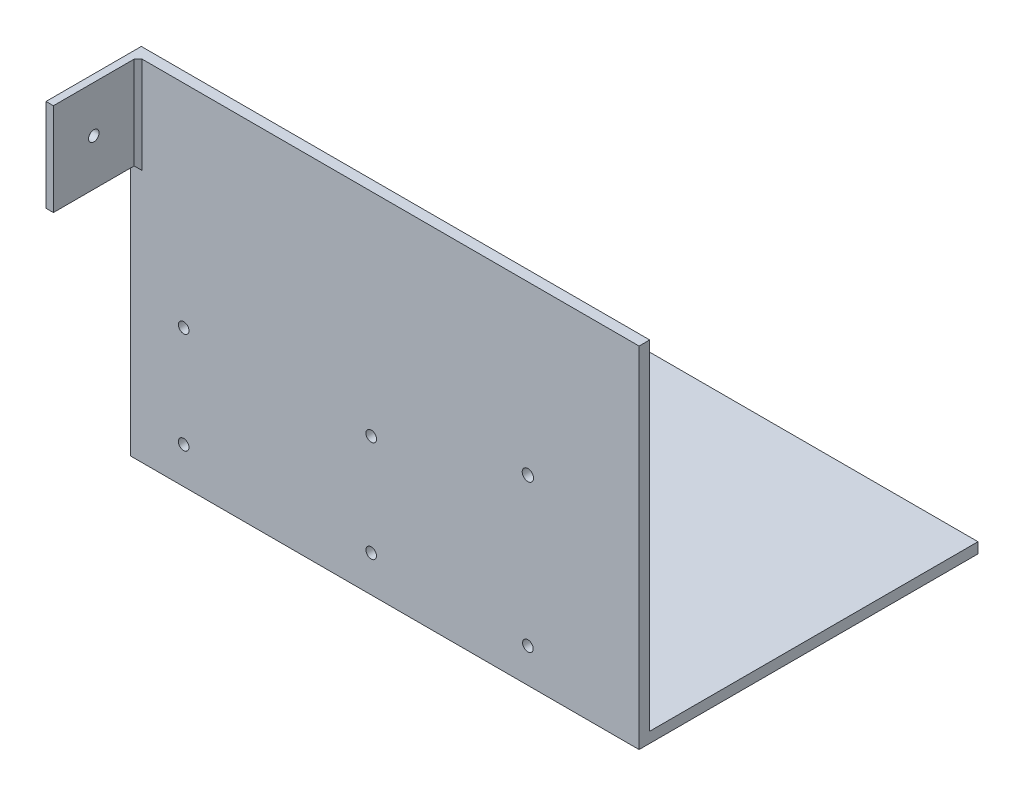
SolidWorks part; units mm, degrees
ref_plane "Front Plane" through (0, 0, 0) normal (0, 0, 1) x (1, 0, 0)
ref_plane "Top Plane" through (0, 0, 0) normal (0, 1, 0) x (1, 0, 0)
ref_plane "Right Plane" through (0, 0, 0) normal (1, 0, 0) x (0, 0, -1)
sketch "Sketch1" plane through (0, 0, 0) normal (0, 1, 0) x (1, 0, 0)
  line L1 (152.4, 101.6) -> (-152.4, 101.6)
  line L2 (152.4, 101.6) -> (152.4, -101.6)
  line L3 (152.4, -101.6) -> (-152.4, -101.6)
  line L4 (-152.4, 101.6) -> (-152.4, -101.6)
  line L5 (152.4, 101.6) -> (-152.4, -101.6) construction
  line L6 (152.4, -101.6) -> (-152.4, 101.6) construction
  point P0 (0, 0)
  dimension "D1" = 304.8
  dimension "D2" = 203.2
extrude "Boss-Extrude1" add sketch "Sketch1" along normal blind 6.35
sketch "Sketch2" plane through (0, 6.35, 0) normal (0, 1, 0) x (1, 0, 0)
  line L0 (152.4, -101.6) -> (152.4, 101.6) construction
  line L6 (-152.4, -101.6) -> (152.4, -101.6)
  line L7 (-152.4, -101.6) -> (-152.4, -95.25)
  line L8 (-152.4, -95.25) -> (152.4, -95.25)
  line L9 (152.4, -101.6) -> (152.4, -95.25)
  dimension "D2" = 6.35
extrude "Boss-Extrude2" add sketch "Sketch2" along normal blind 40.64
sketch "Sketch3" plane through (152.4, 0, 0) normal (1, 0, 0) x (0, 0, -1)
  line L0 (0, 3.4925) -> (0, -3.4925) construction
  line L1 (-101.6, 46.99) -> (-81.1967, 46.99)
  line L2 (-101.6, 46.99) -> (-101.6, 6.35)
  line L3 (-101.6, 6.35) -> (-81.1967, 6.35)
  line L4 (-81.1967, 46.99) -> (-81.1967, 6.35)
  line L5 (101.6, 6.35) -> (81.1967, 6.35)
  line L6 (81.1967, 46.99) -> (81.1967, 6.35)
  line L7 (101.6, 46.99) -> (81.1967, 46.99)
  line L8 (101.6, 46.99) -> (101.6, 6.35)
extrude "Cut-Extrude1" cut sketch "Sketch3" against normal through all
extrude "Boss-Extrude3" add sketch "Sketch2<2>" along normal blind 203.2
sketch "Sketch2<2>" plane through (0, 6.35, 0) normal (0, 1, 0) x (1, 0, 0) same geometry as "Sketch2"
sketch "Sketch9" plane through (0, 0, 0) normal (0, -1, 0) x (1, 0, 0)
  circle A3 centre (-120.65, 79.0786) radius 3.175
  circle A4 centre (-120.65, 18.103) radius 3.175
  circle A7 centre (-8.205, 79.0786) radius 3.175
  circle A8 centre (-8.205, 18.103) radius 3.175
  circle A9 centre (85.7212, 73.6275) radius 3.175
extrude "Cut-Extrude2" cut sketch "Sketch9" against normal blind 10.922
sketch "Sketch10" plane through (0, 0, 101.6) normal (0, 0, 1) x (1, 0, 0)
  circle A4 centre (-120.65, 82.55) radius 3.175
  circle A5 centre (-120.65, 21.8994) radius 3.175
  circle A8 centre (-8.205, 82.4646) radius 3.175
  circle A9 centre (-8.205, 21.8141) radius 3.175
  circle A10 centre (85.7212, 20.5557) radius 3.175
  circle A11 centre (85.7212, 109.2241) radius 3.3928
extrude "Cut-Extrude3" cut sketch "Sketch10" against normal blind 10.922
sketch "Sketch11" plane through (0, 0, 101.6) normal (0, 0, 1) x (1, 0, 0)
  line L1 (-152.4, 209.55) -> (-147.9592, 209.55)
  line L2 (-152.4, 209.55) -> (-152.4, 154.0645)
  line L3 (-152.4, 154.0645) -> (-147.9592, 154.0645)
  line L4 (-147.9592, 209.55) -> (-147.9592, 154.0645)
extrude "Boss-Extrude7" add sketch "Sketch11" along normal blind 50.8
chamfer "Chamfer1" distance 2.38 angle 45 2 edges at (-147.9592, 181.8073, 101.6) (-150.1796, 154.0645, 101.6)
sketch "Sketch12" plane through (0, 0, 0) normal (0, -1, 0) x (1, 0, 0)
  line L1 (-152.4, -101.6) -> (-147.3104, -101.6)
  line L2 (-152.4, -101.6) -> (-152.4, -50.3982)
  line L3 (-152.4, -50.3982) -> (-147.3104, -50.3982)
  line L4 (-147.3104, -101.6) -> (-147.3104, -50.3982)
extrude "Boss-Extrude8" add sketch "Sketch12" along normal blind 50.8
chamfer "Chamfer2" distance 2.38 angle 45 2 edges at (-149.8552, 0, -50.3982) (-147.3104, 0, -75.9991)
sketch "Sketch13" plane through (-147.3104, 0, 0) normal (1, 0, 0) x (0, 0, -1)
  circle A0 centre (75.9991, -26.59) radius 3.175
extrude "Cut-Extrude4" cut sketch "Sketch13" against normal blind 50.8
sketch "Sketch14" plane through (-147.9592, 0, 0) normal (1, 0, 0) x (0, 0, -1)
  circle A0 centre (-128.19, 181.8073) radius 3.175
extrude "Cut-Extrude5" cut sketch "Sketch14" against normal blind 50.8
